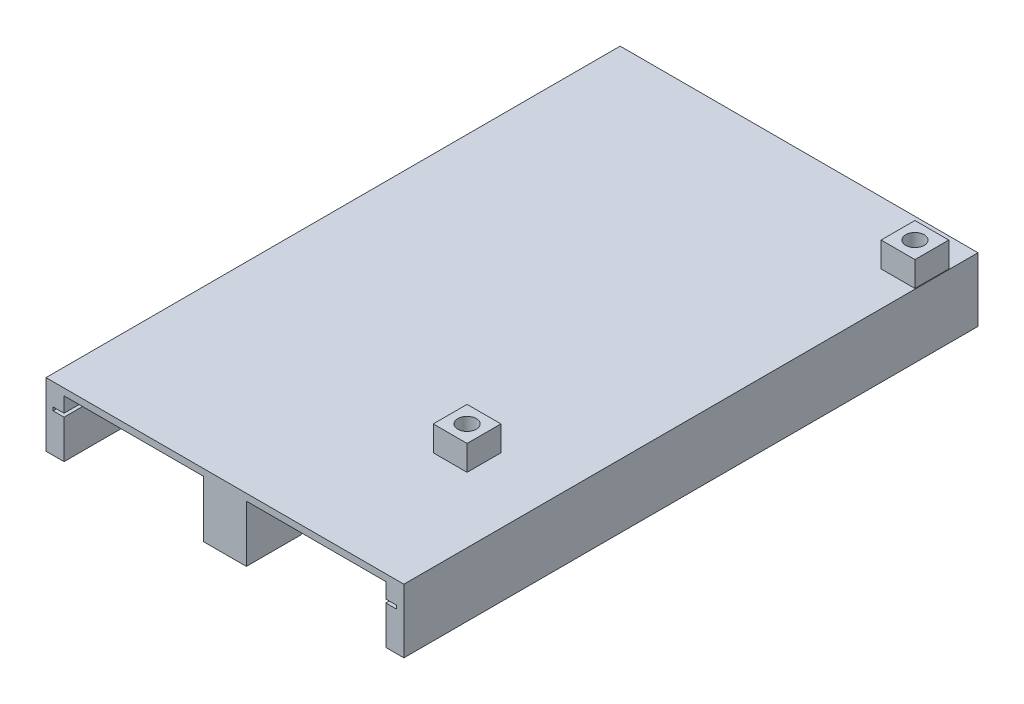
SolidWorks part; units mm, degrees
material "PLA"
ref_plane "Спереди" through (0, 0, 0) normal (0, 0, 1) x (1, 0, 0)
ref_plane "Сверху" through (0, 0, 0) normal (0, 1, 0) x (1, 0, 0)
ref_plane "Справа" through (0, 0, 0) normal (1, 0, 0) x (0, 0, -1)
sketch "Эскиз1" plane through (0, 0, 0) normal (0, 1, 0) x (1, 0, 0)
  line L0 (0, 0) -> (-4740.9496, 0) construction
  line L1 (0, 0) -> (0, -4740.9496) construction
  line L2 (35.675, 63.65) -> (39.675, 63.65)
  line L3 (-35.675, -63.65) -> (-39.675, -63.65)
  line L4 (-35.675, -63.65) -> (-35.675, 63.65)
  line L5 (-35.675, 63.65) -> (-39.675, 63.65)
  line L6 (-39.675, -63.65) -> (-39.675, 63.65)
  line L7 (-35.675, -63.65) -> (-39.675, 63.65) construction
  line L8 (-35.675, 63.65) -> (-39.675, -63.65) construction
  line L9 (39.675, -63.65) -> (39.675, 63.65)
  line L10 (35.675, -63.65) -> (39.675, -63.65)
  line L11 (35.675, -63.65) -> (35.675, 63.65)
  line L12 (35.675, 63.65) -> (39.675, -63.65) construction
  line L13 (35.675, -63.65) -> (39.675, 63.65) construction
  point P5 (-37.675, 0)
  point P14 (37.675, 0)
  dimension "D1" = 4
  dimension "D2" = 127.3
  dimension "D3" = 71.35
extrude "Бобышка-Вытянуть1" add sketch "Эскиз1" along normal blind 12.65
sketch "Эскиз2" plane through (0, 12.65, 0) normal (0, 1, 0) x (1, 0, 0)
  line L1 (39.675, 63.65) -> (-39.675, 63.65)
  line L2 (39.675, 63.65) -> (39.675, -63.65)
  line L3 (39.675, -63.65) -> (-39.675, -63.65)
  line L4 (-39.675, 63.65) -> (-39.675, -63.65)
extrude "Бобышка-Вытянуть2" add sketch "Эскиз2" along normal blind 1.5
sketch "Эскиз3" plane through (0, 0, -63.65) normal (0, 0, -1) x (-1, 0, 0)
  line L0 (0, 0) -> (0, 50000) construction
  line L1 (-35.675, 12.65) -> (-35.675, 0) construction
  line L2 (-35.675, 9.3) -> (-38.075, 9.3)
  line L3 (-35.675, 9.3) -> (-35.675, 8.55)
  line L4 (-35.675, 8.55) -> (-38.075, 8.55)
  line L5 (-38.075, 9.3) -> (-38.075, 8.55)
  line L6 (35.675, 8.55) -> (38.075, 8.55)
  line L7 (38.075, 9.3) -> (38.075, 8.55)
  line L8 (35.675, 9.3) -> (38.075, 9.3)
  line L9 (35.675, 9.3) -> (35.675, 8.55)
  line L10 (-39.675, 0) -> (-35.675, 0) construction
  dimension "D1" = 2.4
  dimension "D2" = 0.75
  dimension "D3" = 8.55
extrude "Вырез-Вытянуть1" cut sketch "Эскиз3" against normal through all from offset 1.5 offset against normal yes
sketch "Эскиз4" plane through (0, 12.65, 0) normal (0, -1, 0) x (1, 0, 0)
  line L0 (35.675, -63.65) -> (35.675, 63.65) construction
  line L1 (-35.675, -63.65) -> (35.675, -63.65)
  line L2 (-35.675, -63.65) -> (-35.675, -62.15)
  line L3 (-35.675, -62.15) -> (35.675, -62.15)
  line L4 (35.675, -63.65) -> (35.675, -62.15)
  dimension "D1" = 1.5
extrude "Бобышка-Вытянуть3" add sketch "Эскиз4" along normal up to surface (12.65 mm away) up to face at (37.675, 0, 0)
sketch "Эскиз6" plane through (0, 12.65, 0) normal (0, -1, 0) x (1, 0, 0)
  line L0 (35.675, -62.15) -> (35.675, 63.65) construction
  line L1 (32.325, -52.35) -> (24.825, -52.35)
  line L2 (32.325, -52.35) -> (32.325, -62.15)
  line L3 (32.325, -59.85) -> (24.825, -59.85) construction
  line L4 (24.825, -52.35) -> (24.825, -62.15)
  line L5 (32.325, -52.35) -> (24.825, -59.85) construction
  line L6 (32.325, -59.85) -> (24.825, -52.35) construction
  line L7 (35.675, -62.15) -> (-35.675, -62.15) construction
  line L8 (32.325, -62.15) -> (24.825, -62.15)
  circle A0 centre (28.575, -56.1) radius 2.1 construction
  point P0 (28.575, -56.1)
  dimension "D3" = 4.2
  dimension "D4" = 1.65
  dimension "D5" = 1.65
  dimension "D1" = 7.1
  dimension "D2" = 6.05
extrude "Бобышка-Вытянуть5" add sketch "Эскиз6" along normal blind 9.6
sketch "Эскиз7" plane through (0, 3.05, 0) normal (0, -1, 0) x (1, 0, 0)
  line L0 (24.825, -52.35) -> (32.325, -59.85) construction
  line L1 (32.325, -52.35) -> (24.825, -59.85) construction
  line L2 (32.325, -62.15) -> (32.325, -52.35) construction
  line L3 (24.825, -52.35) -> (24.825, -62.15) construction
  circle A0 centre (28.575, -56.1) radius 2.05
  dimension "D1" = 4.1
extrude "Вырез-Вытянуть2" cut sketch "Эскиз7" against normal blind 4.5
sketch "Эскиз8" plane through (0, 0, 0) normal (0, -1, 0) x (1, 0, 0)
  line L0 (-35.675, 63.65) -> (-35.675, -62.15) construction
  line L1 (-35.675, 38.05) -> (-38.075, 38.05)
  line L2 (-35.675, 38.05) -> (-35.675, 32.2)
  line L3 (-35.675, 32.2) -> (-38.075, 32.2)
  line L4 (-38.075, 38.05) -> (-38.075, 32.2)
  line L5 (0, 0) -> (0, 50000) construction
  line L6 (-35.675, -16.55) -> (-38.075, -16.55)
  line L7 (-35.675, -16.55) -> (-35.675, -22.4)
  line L8 (-35.675, -22.4) -> (-38.075, -22.4)
  line L9 (-38.075, -16.55) -> (-38.075, -22.4)
  line L10 (-39.675, 63.65) -> (-35.675, 63.65) construction
  line L11 (35.675, -22.4) -> (38.075, -22.4)
  line L12 (38.075, -16.55) -> (38.075, -22.4)
  line L13 (35.675, -16.55) -> (38.075, -16.55)
  line L14 (35.675, -16.55) -> (35.675, -22.4)
  line L15 (35.675, 32.2) -> (38.075, 32.2)
  line L16 (38.075, 38.05) -> (38.075, 32.2)
  line L17 (35.675, 38.05) -> (38.075, 38.05)
  line L18 (35.675, 38.05) -> (35.675, 32.2)
  line L19 (39.675, -63.65) -> (-39.675, -63.65) construction
  point P26 (0, -63.65)
  dimension "D1" = 2.4
  dimension "D2" = 5.85
  dimension "D3" = 48.75
  dimension "D4" = 25.6
extrude "Вырез-Вытянуть3" cut sketch "Эскиз8" against normal up to surface (8.55 mm away) up to face at (-36.875, 8.55, 0.75)
sketch "Эскиз10" plane through (0, 12.65, 0) normal (0, -1, 0) x (1, 0, 0)
  line L0 (-35.675, 63.65) -> (-35.675, -62.15) construction
  line L1 (-25.275, -51.75) -> (-28.275, -51.75)
  line L2 (-25.275, -51.75) -> (-25.275, -57.7)
  line L3 (-25.275, -57.7) -> (-28.275, -57.7)
  line L4 (-28.275, -51.75) -> (-28.275, -57.7)
  line L5 (24.825, -62.15) -> (-35.675, -62.15) construction
  line L6 (35.675, -62.15) -> (-35.675, -62.15) construction
  line L8 (15.225, -51.75) -> (18.225, -51.75)
  line L9 (15.225, -51.75) -> (15.225, -57.7)
  line L10 (15.225, -57.7) -> (18.225, -57.7)
  line L11 (18.225, -51.75) -> (18.225, -57.7)
  dimension "D1" = 10.4
  dimension "D2" = 4.45
  dimension "D3" = 10.4
  dimension "D4" = 3
  dimension "D5" = 50.9
extrude "Бобышка-Вытянуть6" add sketch "Эскиз10" along normal blind 3.95
sketch "Эскиз11" plane through (0, 12.65, 0) normal (0, -1, 0) x (1, 0, 0)
  line L1 (-25.275, -57.7) -> (15.225, -57.7)
  line L2 (-25.275, -57.7) -> (-25.275, -51.75)
  line L3 (-25.275, -51.75) -> (15.225, -51.75)
  line L4 (15.225, -57.7) -> (15.225, -51.75)
extrude "Бобышка-Вытянуть7" add sketch "Эскиз11" along normal blind 0.35
fillet "Скругление4" radius 4 1 edges at (-5.025, 12.65, -57.7)
fillet "Скругление5" radius 2 2 edges at (-26.775, 8.7, -57.7) (16.725, 8.7, -57.7)
sketch "Эскиз12" plane through (0, 0, -62.15) normal (0, 0, 1) x (1, 0, 0)
  line L0 (24.825, 12.65) -> (-35.675, 12.65) construction
  line L1 (15.475, 8) -> (-25.525, 8)
  line L2 (15.475, 8) -> (15.475, 12.65)
  line L12 (15.475, 12.65) -> (-25.525, 12.65)
  line L13 (-25.525, 8) -> (-25.525, 12.65)
  line L15 (-5.025, 12.3) -> (-5.025, 12.65) construction
  line L17 (-25.275, 12.3) -> (15.225, 12.3) construction
  point P13 (-5.025, 12.3)
  dimension "D1" = 4.65
  dimension "D2" = 41
extrude "Вырез-Вытянуть4" cut sketch "Эскиз12" against normal through all
sketch "Эскиз13" plane through (0, 12.65, 0) normal (0, -1, 0) x (1, 0, 0)
  line L0 (0, 63.65) -> (0, 50063.65) construction
  line L1 (-35.675, 63.65) -> (35.675, 63.65) construction
  line L2 (-4.75, 60.9) -> (-4.75, 63.65)
  line L3 (4.75, 60.9) -> (-4.75, 60.9) construction
  line L4 (4.75, 60.9) -> (4.75, 51.4)
  line L5 (4.75, 51.4) -> (-4.75, 51.4)
  line L6 (-4.75, 60.9) -> (-4.75, 51.4)
  line L7 (4.75, 60.9) -> (-4.75, 51.4) construction
  line L8 (4.75, 51.4) -> (-4.75, 60.9) construction
  line L9 (-4.75, 63.65) -> (4.75, 63.65)
  line L10 (4.75, 63.65) -> (4.75, 60.9)
  circle A0 centre (0, 56.15) radius 2.75 construction
  point P4 (0, 63.65)
  point P5 (0, 56.15)
  dimension "D1" = 5.5
  dimension "D2" = 9.5
  dimension "D3" = 7.5
extrude "Бобышка-Вытянуть8" add sketch "Эскиз13" along normal blind 12.55
sketch "Эскиз14" plane through (0, 0.1, 0) normal (0, -1, 0) x (1, 0, 0)
  line L0 (-4.75, 60.9) -> (4.75, 51.4) construction
  line L1 (4.75, 60.9) -> (-4.75, 51.4) construction
  line L2 (4.75, 51.4) -> (4.75, 63.65) construction
  line L3 (-4.75, 63.65) -> (-4.75, 51.4) construction
  line L4 (-4.75, 60.9) -> (4.75, 60.9) construction
  circle A0 centre (0, 56.15) radius 2.05
  dimension "D1" = 4.1
extrude "Вырез-Вытянуть5" cut sketch "Эскиз14" against normal blind 7
sketch "Эскиз15" plane through (0, 14.15, 0) normal (0, 1, 0) x (1, 0, 0)
  line L0 (39.675, -63.65) -> (39.675, 63.65) construction
  line L1 (32.0454, 57.2971) -> (39.5454, 57.2971)
  line L2 (32.0454, 57.2971) -> (32.0454, 49.7971)
  line L3 (32.0454, 49.7971) -> (39.5454, 49.7971)
  line L4 (39.5454, 57.2971) -> (39.5454, 49.7971)
  line L5 (32.0454, 57.2971) -> (39.5454, 49.7971) construction
  line L6 (32.0454, 49.7971) -> (39.5454, 57.2971) construction
  line L7 (17.7005, -27.6612) -> (25.2005, -27.6612)
  line L8 (17.7005, -27.6612) -> (17.7005, -35.1612)
  line L9 (17.7005, -35.1612) -> (25.2005, -35.1612)
  line L10 (25.2005, -27.6612) -> (25.2005, -35.1612)
  line L11 (17.7005, -27.6612) -> (25.2005, -35.1612) construction
  line L12 (17.7005, -35.1612) -> (25.2005, -27.6612) construction
  line L13 (-39.675, -63.65) -> (39.675, -63.65) construction
  point P0 (35.7954, 53.5471)
  point P5 (21.4505, -31.4112)
  dimension "D1" = 7.5
  dimension "D2" = 18.2245
  dimension "D3" = 32.2388
  dimension "D4" = 3.8796
  dimension "D5" = 117.1971
extrude "Бобышка-Вытянуть9" add sketch "Эскиз15" along normal blind 5.55
sketch "Эскиз16" plane through (0, 19.7, 0) normal (0, 1, 0) x (1, 0, 0)
  line L0 (32.0454, 57.2971) -> (39.5454, 49.7971) construction
  line L1 (39.5454, 57.2971) -> (32.0454, 49.7971) construction
  line L2 (25.2005, -27.6612) -> (17.7005, -35.1612) construction
  line L3 (17.7005, -27.6612) -> (25.2005, -35.1612) construction
  circle A0 centre (21.4505, -31.4112) radius 2.05
  circle A1 centre (35.7954, 53.5471) radius 2.05
  dimension "D1" = 4.1
extrude "Вырез-Вытянуть6" cut sketch "Эскиз16" against normal blind 5
